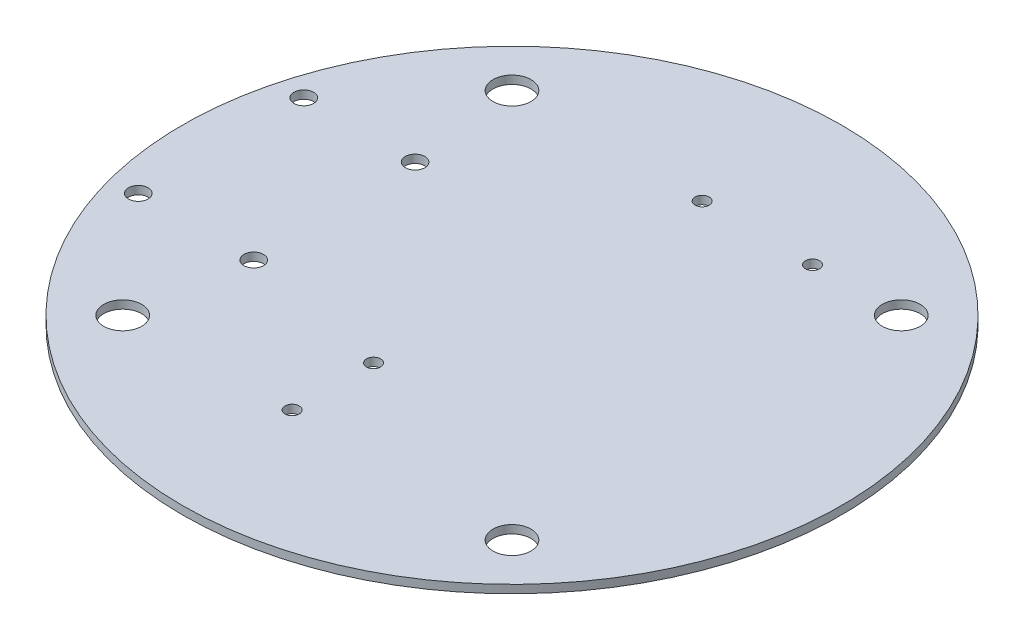
SolidWorks part; units mm, degrees
ref_plane "Front Plane" through (0, 0, 0) normal (0, 0, 1) x (1, 0, 0)
ref_plane "Top Plane" through (0, 0, 0) normal (0, 1, 0) x (1, 0, 0)
ref_plane "Right Plane" through (0, 0, 0) normal (1, 0, 0) x (0, 0, -1)
sketch "Sketch1" plane through (0, 0, 0) normal (0, 1, 0) x (1, 0, 0)
  circle A0 centre (0, 0) radius 60.7
  dimension "PCBdiam" = 121.4
extrude "Boss-Extrude1" add sketch "Sketch1" along normal blind 1.5
hole_wizard "M6 Clearance Hole1" positions "Sketch2" profile "Sketch4" hole size "M6" standard "ANSI Metric" end condition through all
sketch "Sketch2" plane through (0, 1.5, 0) normal (0, 1, 0) x (1, 0, 0)
  line L0 (0, 0) -> (-28.5457, 28.5457) construction
  line L1 (-35.8503, -35.8503) -> (0, 0) construction
  line L3 (0, 0) -> (-73.422, 0) construction
  circle A0 centre (0, 0) radius 60.7 construction
  ellipse E2 centre (-116.4291, -176.9435) end of major axis (-117.7556, -176.0714) minor radius 1.3748
  ellipse E3 centre (-116.4291, -176.9435) end of major axis (-115.1026, -177.8157) minor radius 1.3748
  point P7 (-35.8503, -35.8503)
  dimension "D1" = 0
  dimension "holeRadius" = 50.7
  dimension "D2" = 45
sketch "Sketch4" plane through (-35.8503, 1.5, 35.8503) normal (1, 0, 0) x (0, 0, 1)
  line L0 (0, 0) -> (0, 1.5)
  line L1 (0, 1.5) -> (3.5, 1.5)
  line L2 (3.5, 1.5) -> (3.5, 0)
  line L5 (3.5, 0) -> (0, 0)
  line L11 (0, -6.35) -> (0, 107.95) construction
  dimension "Thru Hole Dia." = 7
  dimension "Thru Hole Depth" = 1.5
pattern_circular "CirPattern1" count 4 over 360 about axis through (0, 1.5, 0) along (0, -1, 0) of "M6 Clearance Hole1"
sketch "Teensy Outline" plane through (0, 1.5, 0) normal (0, 1, 0) x (1, 0, 0)
  line L1 (-27.654, 45.7) -> (-10, 45.7)
  line L2 (-27.654, 45.7) -> (-27.654, -12.72)
  line L3 (-27.654, -12.72) -> (-10, -12.72)
  line L4 (-10, 45.7) -> (-10, -12.72)
  circle A1 centre (0, 0) radius 60.7 construction
  dimension "D1" = 17.654
  dimension "D2" = 58.42
  dimension "D3" = 10
  dimension "D4" = 15
sketch "BMP390 Outline" plane through (0, 1.5, 0) normal (0, 1, 0) x (1, 0, 0)
  line L0 (19.61, 49.7) -> (-3.25, 49.7) construction
  line L2 (22.15, 51.04) -> (-3.25, 51.04)
  line L3 (-3.25, 51.04) -> (-3.25, 33.26)
  line L4 (22.15, 33.26) -> (-3.25, 33.26)
  line L6 (22.15, 51.04) -> (22.15, 33.26)
  line L7 (19.61, 49.7) -> (19.61, 33.26) construction
  line L8 (-27.654, 45.7) -> (-10, 45.7) construction
  line L9 (-10, 45.7) -> (-10, -12.72) construction
  dimension "D1" = 17.78
  dimension "D2" = 25.4
  dimension "D3" = 1.34
  dimension "D4" = 4
  dimension "D5" = 6.75
  dimension "D6" = 5.08
sketch "NEO-6M Outline" plane through (0, 1.5, 0) normal (0, 1, 0) x (1, 0, 0)
  line L0 (-48.84, 17.78) -> (-48.84, 15.24) construction
  line L1 (-56.34, 17.78) -> (-30, 17.78)
  line L2 (-56.34, 17.78) -> (-56.34, -17.78)
  line L3 (-56.34, -17.78) -> (-30, -17.78)
  line L4 (-30, 17.78) -> (-30, -17.78)
  line L5 (-48.84, 15.24) -> (-37.5, 15.24) construction
  line L6 (-37.5, 15.24) -> (-37.5, 17.78) construction
  point P4 (-30, 0)
  point P9 (-43.17, 15.24)
  point P11 (-43.17, 17.78)
  dimension "D1" = 26.34
  dimension "D2" = 35.56
  dimension "D3" = 30
  dimension "D4" = 7.5
  dimension "D5" = 2.54
sketch "Accel, gyro outline" plane through (0, 1.5, 0) normal (0, 1, 0) x (1, 0, 0)
  line L0 (47.32, 26.44) -> (27, 26.44) construction
  line L1 (52.4, 27.78) -> (27, 27.78)
  line L2 (27, 27.78) -> (27, 10)
  line L3 (52.4, 10) -> (27, 10)
  line L4 (52.4, 27.78) -> (52.4, 10)
  line L5 (47.32, 26.44) -> (47.32, 11.34) construction
  line L6 (27, 18.89) -> (52.4, 18.89) construction
  line L7 (47.32, 11.34) -> (27, 11.34) construction
  dimension "D1" = 17.78
  dimension "D2" = 25.4
  dimension "D3" = 1.34
  dimension "D4" = 5.08
  dimension "D5" = 10
  dimension "D6" = 27
sketch "Airspeed sensor outline" plane through (0, 1.5, 0) normal (0, 1, 0) x (1, 0, 0)
  line L0 (-22.654, -23.8503) -> (-29.154, -23.8503) construction
  line L1 (-22.654, -17.8503) -> (-2.654, -17.8503)
  line L2 (-22.654, -17.8503) -> (-22.654, -37.8503)
  line L3 (-22.654, -37.8503) -> (-2.654, -37.8503)
  line L4 (-2.654, -17.8503) -> (-2.654, -37.8503)
  line L5 (-29.154, -23.8503) -> (-29.154, -31.8503) construction
  line L6 (-29.154, -31.8503) -> (-22.654, -31.8503) construction
  line L7 (-27.654, 45.7) -> (-27.654, -12.72) construction
  circle A0 centre (-35.8503, -35.8503) radius 3.5 construction
  point P8 (-29.154, -27.8503)
  point P9 (-22.654, -27.8503)
  dimension "D1" = 20
  dimension "D2" = 20
  dimension "D3" = 6.5
  dimension "D4" = 8
  dimension "D5" = 5
  dimension "D6" = 2
sketch "Xbee outline" plane through (0, 1.5, 0) normal (0, 1, 0) x (1, 0, 0)
  line L0 (9.25, 2.26) -> (9.25, -14.74) construction
  line L1 (4.625, -14.74) -> (13.875, -14.74)
  line L2 (13.875, -14.74) -> (21.5, -8.24)
  line L3 (21.5, -8.24) -> (21.5, 18.26)
  line L4 (21.5, 18.26) -> (-3, 18.26)
  line L5 (-3, -8.24) -> (-3, 18.26)
  line L6 (4.625, -14.74) -> (-3, -8.24)
  line L7 (9.25, -20.0658) -> (9.25, -49.74) construction
  line L8 (22.15, 33.26) -> (-3.25, 33.26) construction
  line L9 (-10, 45.7) -> (-10, -12.72) construction
  line L10 (14.75, -49.74) -> (14.75, -14.74) construction
  line L11 (14.75, -49.74) -> (3.75, -49.74) construction
  line L12 (3.75, -49.74) -> (3.75, -14.74) construction
  line L13 (14.75, -14.74) -> (3.75, -14.74) construction
  point P7 (9.25, 18.26)
  point P11 (9.25, -14.74)
  point P12 (0, 0)
  point P13 (-1.6024, -57.8922)
  point P14 (17.9175, -11.3479)
  point P15 (73.0998, 0)
  point P16 (-4.5418, 23.6485)
  point P17 (0, 0)
  point P18 (0, 0)
  point P25 (-3.5387, 20.6897)
  point P28 (0, 0)
  point P29 (9.25, -21.3757)
  point P30 (0, 0)
  point P31 (9.25, -20.0658)
  point P32 (9.25, -49.74)
  point P33 (0, 0)
  dimension "D1" = 24.5
  dimension "D2" = 33
  dimension "D3" = 26.5
  dimension "D4" = 9.25
  dimension "D5" = 16
  dimension "D6" = 35
  dimension "D7" = 11
  dimension "D8" = 0
  dimension "D9" = 15
  dimension "D10" = 7
hole_wizard "M2 Clearance Hole1" positions "Sketch20" profile "Sketch19" hole size "M2" standard "ANSI Metric" end condition through all
sketch "Sketch20" plane through (0, 1.5, 0) normal (0, 1, 0) x (1, 0, 0)
  circle A0 centre (-0.71, 35.73) radius 1.2493 construction
  circle A1 centre (19.61, 35.73) radius 1.2493 construction
  circle A2 centre (-5.154, -20.3503) radius 1.25 construction
  circle A3 centre (-5.154, -20.3503) radius 1.25 construction
  circle A4 centre (-5.154, -35.3503) radius 1.25 construction
  circle A5 centre (-5.154, -35.3503) radius 1.25 construction
  point P1 (-0.71, 35.73)
  point P7 (19.61, 35.73)
  point P13 (-5.154, -20.3503)
  point P16 (-5.154, -35.3503)
sketch "Sketch19" plane through (-0.71, 1.5, -35.73) normal (1, 0, 0) x (0, 0, 1)
  line L0 (0, 0) -> (0, 1.5)
  line L1 (0, 1.5) -> (1.3, 1.5)
  line L2 (1.3, 1.5) -> (1.3, 0)
  line L5 (1.3, 0) -> (0, 0)
  line L11 (0, -6.35) -> (0, 107.95) construction
  dimension "Thru Hole Dia." = 2.6
  dimension "Thru Hole Depth" = 1.5
hole_wizard "M3 Clearance Hole2" positions "Sketch21" profile "Sketch22" hole size "M3" standard "ANSI Metric" end condition through all
sketch "Sketch21" plane through (0, 1.5, 0) normal (0, 1, 0) x (1, 0, 0)
  point P0 (-53.8645, 15.5117)
  point P3 (-53.8645, -14.9683)
  point P6 (-32.6045, -14.9683)
  point P9 (-33.3665, 15.5117)
sketch "Sketch22" plane through (-53.8645, 1.5, -15.5117) normal (1, 0, 0) x (0, 0, 1)
  line L0 (0, 0) -> (0, 1.5)
  line L1 (0, 1.5) -> (1.8, 1.5)
  line L2 (1.8, 1.5) -> (1.8, 0)
  line L5 (1.8, 0) -> (0, 0)
  line L11 (0, -6.35) -> (0, 107.95) construction
  dimension "Thru Hole Dia." = 3.6
  dimension "Thru Hole Depth" = 1.5
